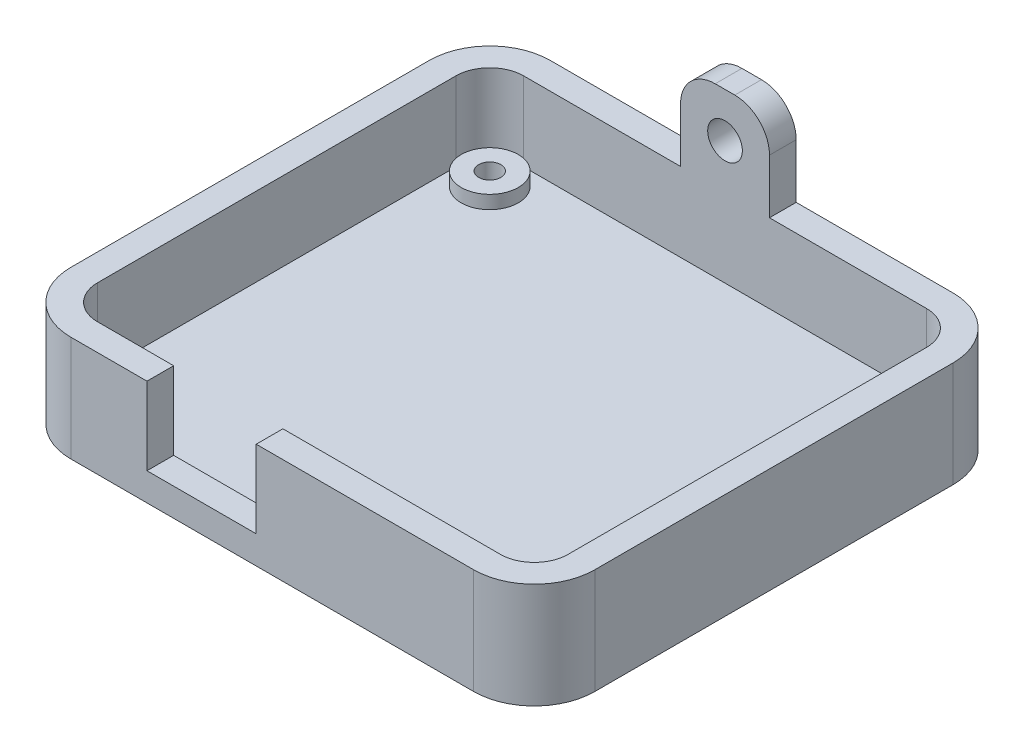
SolidWorks part; units mm, degrees
ref_plane "Front Plane" through (0, 0, 0) normal (0, 0, 1) x (1, 0, 0)
ref_plane "Top Plane" through (0, 0, 0) normal (0, 1, 0) x (1, 0, 0)
ref_plane "Right Plane" through (0, 0, 0) normal (1, 0, 0) x (0, 0, -1)
sketch "Sketch1" plane through (0, 0, 0) normal (0, 1, 0) x (1, 0, 0)
  line L0 (3.81, 3) -> (49.09, 3)
  line L1 (3.81, 0) -> (49.09, 0)
  line L2 (0, -3.81) -> (0, -44.09)
  line L3 (3.81, -47.9) -> (49.09, -47.9)
  line L4 (52.9, -3.81) -> (52.9, -44.09)
  line L5 (55.9, -3.81) -> (55.9, -44.09)
  line L6 (3.81, -50.9) -> (49.09, -50.9)
  line L7 (-3, -3.81) -> (-3, -44.09)
  arc A0 (52.9, -3.81) -> (49.09, 0) centre (49.09, -3.81) ccw
  arc A1 (0, -3.81) -> (3.81, 0) centre (3.81, -3.81) cw
  arc A2 (3.81, -47.9) -> (0, -44.09) centre (3.81, -44.09) cw
  arc A3 (52.9, -44.09) -> (49.09, -47.9) centre (49.09, -44.09) cw
  circle A4 centre (49.09, -44.09) radius 1.25
  circle A5 centre (3.81, -44.09) radius 1.25
  circle A6 centre (3.81, -3.81) radius 1.25
  circle A7 centre (49.09, -3.81) radius 1.25
  arc A8 (55.9, -3.81) -> (49.09, 3) centre (49.09, -3.81) ccw
  arc A9 (55.9, -44.09) -> (49.09, -50.9) centre (49.09, -44.09) cw
  arc A10 (3.81, -50.9) -> (-3, -44.09) centre (3.81, -44.09) cw
  arc A11 (-3, -3.81) -> (3.81, 3) centre (3.81, -3.81) cw
  circle A12 centre (3.81, -3.81) radius 3.21
  circle A13 centre (49.09, -3.81) radius 3.21
  circle A14 centre (49.09, -44.09) radius 3.21
  circle A15 centre (3.81, -44.09) radius 3.21
  point P7 (52.9, 0)
  point P10 (0, 0)
  point P15 (52.9, -47.9)
  dimension "D3" = 3.81
  dimension "D4" = 3.81
  dimension "D5" = 3.81
  dimension "D6" = 3.81
  dimension "D7" = 3
  dimension "D8" = 2.5
  dimension "D9" = 2.5
  dimension "D10" = 2.5
  dimension "D11" = 2.5
  dimension "D12" = 6.42
  dimension "D13" = 6.42
  dimension "D14" = 6.42
  dimension "D15" = 6.42
  dimension "D1" = 52.9
  dimension "D2" = 47.9
extrude "Boss-Extrude1" add sketch "Sketch1" against normal blind 3 contours L7 A10 L6 A9 L5 A8 L0 A11
extrude "Cut-Extrude1" cut sketch "Sketch1<3>" against normal up to next contours A6 | A5 | A4 | A7 region at (49.09, 0, 44.09) region at (3.81, 0, 44.09) region at (3.81, 0, 3.81) region at (49.09, 0, 3.81)
sketch "Sketch1<3>" plane through (0, 0, 0) normal (0, 1, 0) x (1, 0, 0) same geometry as "Sketch1"
extrude "Boss-Extrude2" add sketch "Sketch1<4>" along normal blind 8.86 contours A11 L7 A10 L6 A9 L5 A8 L0 L4 A3 L3 A2 L2 A1 L1 A0 region at (26.45, 0, -2.2016)
sketch "Sketch1<4>" plane through (0, 0, 0) normal (0, 1, 0) x (1, 0, 0) same geometry as "Sketch1"
extrude "Boss-Extrude3" add sketch "Sketch1<5>" along normal blind 1.5 contours A13 A7 | A14 A4 | A15 A5 | A12 A6 region at (0.6908, 0, 3.81) region at (45.9708, 0, 3.81) region at (45.9708, 0, 44.09) region at (0.6908, 0, 44.09)
sketch "Sketch1<5>" plane through (0, 0, 0) normal (0, 1, 0) x (1, 0, 0) same geometry as "Sketch1"
sketch "Sketch2" plane through (0, 0, 50.9) normal (0, 0, 1) x (1, 0, 0)
  line L0 (3.81, -3) -> (49.09, -3) construction
  line L1 (12.36, 8.865) -> (24.64, 8.865)
  line L2 (12.36, 8.865) -> (12.36, 0.135)
  line L3 (12.36, 0.135) -> (24.64, 0.135)
  line L4 (24.64, 8.865) -> (24.64, 0.135)
  line L5 (-3, -3) -> (-3, 8.86) construction
  dimension "D1" = 3.135
  dimension "D2" = 8.73
  dimension "D3" = 12.28
  dimension "D4" = 15.36
extrude "Cut-Extrude2" cut sketch "Sketch2" against normal blind 3
sketch "Sketch5" plane through (0, 0, -3) normal (0, 0, -1) x (-1, 0, 0)
  line L0 (-3.81, 8.86) -> (-49.09, 8.86) construction
  line L1 (-31.45, 8.86) -> (-21.45, 8.86)
  line L2 (-31.45, 8.86) -> (-31.45, 14.96)
  line L3 (-27.55, 18.86) -> (-25.35, 18.86)
  line L4 (-21.45, 8.86) -> (-21.45, 14.96)
  line L5 (-55.9, -3) -> (-55.9, 8.86) construction
  arc A0 (-31.45, 14.96) -> (-27.55, 18.86) centre (-27.55, 14.96) cw
  arc A1 (-21.45, 14.96) -> (-25.35, 18.86) centre (-25.35, 14.96) ccw
  circle A2 centre (-26.45, 13.86) radius 1.95
  point P8 (-31.45, 18.86)
  point P11 (-21.45, 18.86)
  point P18 (-27.2074, 15.5218)
  point P19 (-28.7222, 17.7309)
  dimension "D3" = 3.9
  dimension "D4" = 3.9
  dimension "D6" = 3.9
  dimension "D1" = 10
  dimension "D2" = 10
  dimension "D5" = 24.45
  dimension "D7" = 5
  dimension "D8" = 5
extrude "Boss-Extrude5" add sketch "Sketch5" against normal blind 3
